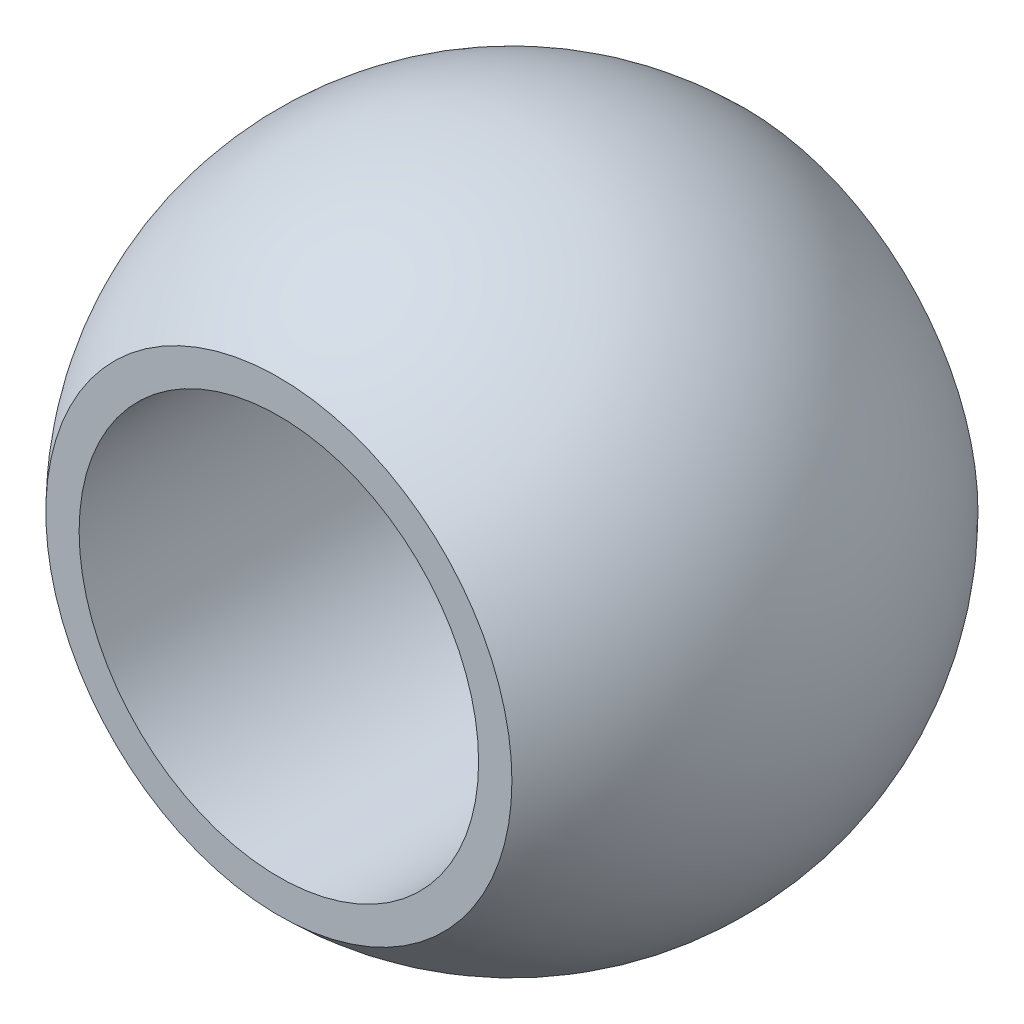
SolidWorks part; units mm, degrees
material "AISI 304"
ref_plane "Front" through (0, 0, 0) normal (0, 0, 1) x (1, 0, 0)
ref_plane "Top" through (0, 0, 0) normal (0, 1, 0) x (1, 0, 0)
ref_plane "Right" through (0, 0, 0) normal (1, 0, 0) x (0, 0, -1)
sketch "Sketch1" plane through (0, 0, 0) normal (0, 0, 1) x (1, 0, 0)
  line L0 (0, 9.9) -> (0, -9.9) construction
  line L1 (0, 9.9) -> (0, -9.9)
  arc A0 (0, 9.9) -> (0, -9.9) centre (0, 0) cw
  dimension "D1" = 9.9
revolve "Revolve1" add sketch "Sketch1" angle 360 about L0
sketch "Sketch2" plane through (0, 0, 0) normal (0, 0, 1) x (1, 0, 0)
  circle A0 centre (0, 0) radius 6
extrude "Cut-Extrude1" cut sketch "Sketch2" against normal blind 22 and the other way blind 22
sketch "Sketch3" plane through (0, 0, 0) normal (0, 1, 0) x (1, 0, 0)
  line L0 (-11.087, 7) -> (11.4574, 7)
  line L1 (11.4574, 7) -> (11.4574, 10.2997)
  line L2 (11.4574, 10.2997) -> (-11.087, 10.2997)
  line L3 (-11.087, 10.2997) -> (-11.087, 7)
  line L4 (-11.0908, -7) -> (11.4574, -7)
  line L5 (11.4574, -7) -> (11.4574, -9.7498)
  line L6 (11.4574, -9.7498) -> (-11.0908, -9.7498)
  line L7 (-11.0908, -9.7498) -> (-11.0908, -7)
  dimension "D1" = 7
  dimension "D2" = 7
extrude "Cut-Extrude2" cut sketch "Sketch3" against normal blind 10 and the other way blind 10
